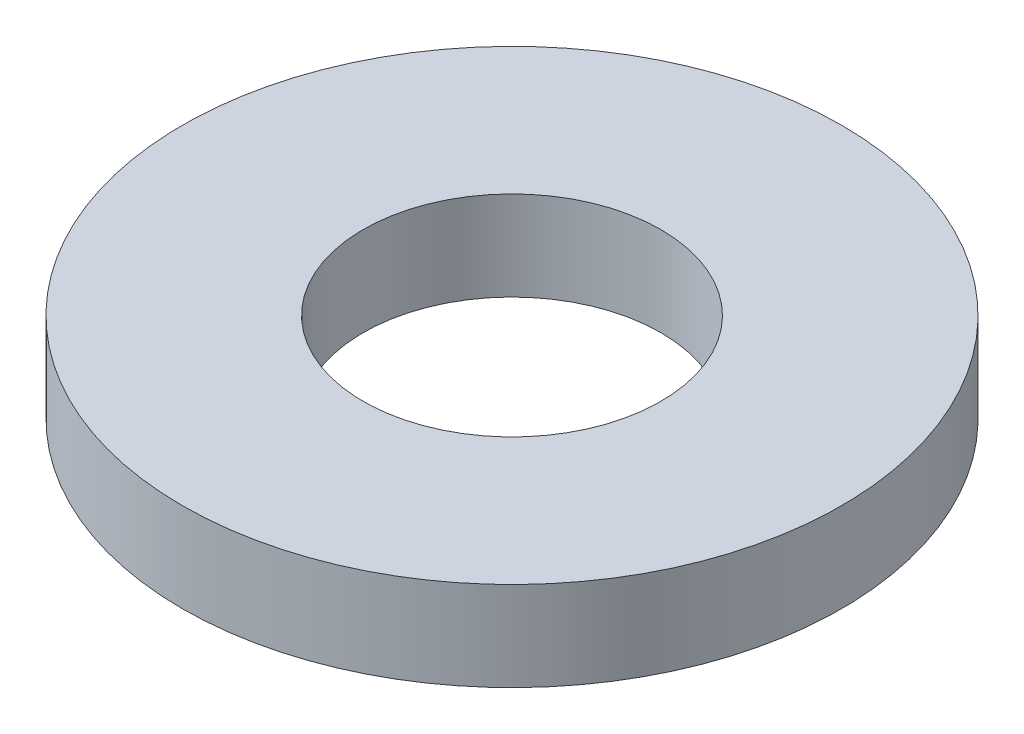
SolidWorks part; units mm, degrees
ref_plane "Front Plane" through (0, 0, 0) normal (0, 0, 1) x (1, 0, 0)
ref_plane "Top Plane" through (0, 0, 0) normal (0, 1, 0) x (1, 0, 0)
ref_plane "Right Plane" through (0, 0, 0) normal (1, 0, 0) x (0, 0, -1)
sketch "Sketch1" plane through (0, 0, 0) normal (0, 1, 0) x (1, 0, 0)
  circle A0 centre (0, 0) radius 77.5
  dimension "FLANGE_OD" = 155
extrude "Boss-Extrude1" add sketch "Sketch1" along normal blind 21
sketch "Sketch2" plane through (0, 0, 0) normal (0, 1, 0) x (1, 0, 0)
  circle A0 centre (0, 0) radius 35
  dimension "BORE_D" = 70
extrude "Cut-Extrude1" cut sketch "Sketch2" along normal through all
sketch "Sketch3" plane through (0, 21, 0) normal (0, 1, 0) x (1, 0, 0)
  circle A0 centre (0, 0) radius 28.1342 construction
  circle A1 centre (-28.1342, 0) radius 5.7842
  dimension "BOLT_D" = 11.5684
  dimension "BOLT_PCD" = 56.2684
extrude "Cut-Extrude2" cut sketch "Sketch3" against normal blind 20.1745 rebuild error yes
pattern_circular "CirPattern1" count 5 over 360 rebuild error yes
